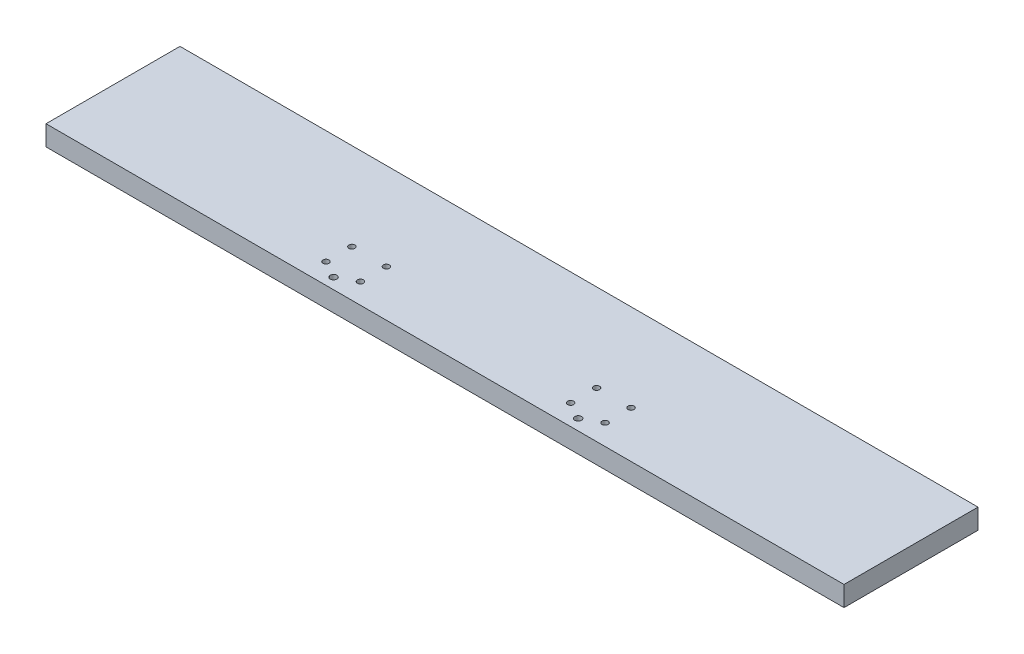
SolidWorks part; units mm, degrees
ref_plane "Front Plane" through (0, 0, 0) normal (0, 0, 1) x (1, 0, 0)
ref_plane "Top Plane" through (0, 0, 0) normal (0, 1, 0) x (1, 0, 0)
ref_plane "Right Plane" through (0, 0, 0) normal (1, 0, 0) x (0, 0, -1)
sketch "Sketch2" plane through (0, 0, 0) normal (0, 1, 0) x (1, 0, 0)
  line L1 (0, 0) -> (756.412, 0)
  line L2 (0, 0) -> (0, 127)
  line L3 (0, 127) -> (756.412, 127)
  line L4 (756.412, 0) -> (756.412, 127)
  dimension "D1" = 127
  dimension "D2" = 756.412
extrude "Boss-Extrude1" add sketch "Sketch2" along normal blind 19.05
sketch "Sketch3" plane through (0, 19.05, 0) normal (0, 1, 0) x (1, 0, 0)
  circle A0 centre (245.9291, 19.4628) radius 2.8511
  circle A1 centre (278.5808, 19.4628) radius 2.8511
  circle A2 centre (278.5808, 44.0373) radius 2.8511
  circle A3 centre (245.9291, 44.0373) radius 2.8511
  circle A4 centre (477.8311, 19.4628) radius 2.8511
  circle A5 centre (510.4828, 19.4628) radius 2.8511
  circle A6 centre (510.4828, 44.0373) radius 2.8511
  circle A7 centre (477.8311, 44.0373) radius 2.8511
extrude "Cut-Extrude1" cut sketch "Sketch3" against normal up to next
sketch "Sketch4" plane through (0, 19.05, 0) normal (0, 1, 0) x (1, 0, 0)
  line L0 (262.255, 12.7) -> (262.255, 10.3188) construction
  line L2 (494.157, 12.7) -> (494.157, 10.3188) construction
  circle A0 centre (494.157, 10.3188) radius 3.175
  circle A1 centre (262.255, 10.3188) radius 3.175
  dimension "D1" = 6.35
  dimension "D3" = 6.35
  dimension "D2" = 2.3813
  dimension "D4" = 2.3813
extrude "Cut-Extrude2" cut sketch "Sketch4" against normal blind 6.35
